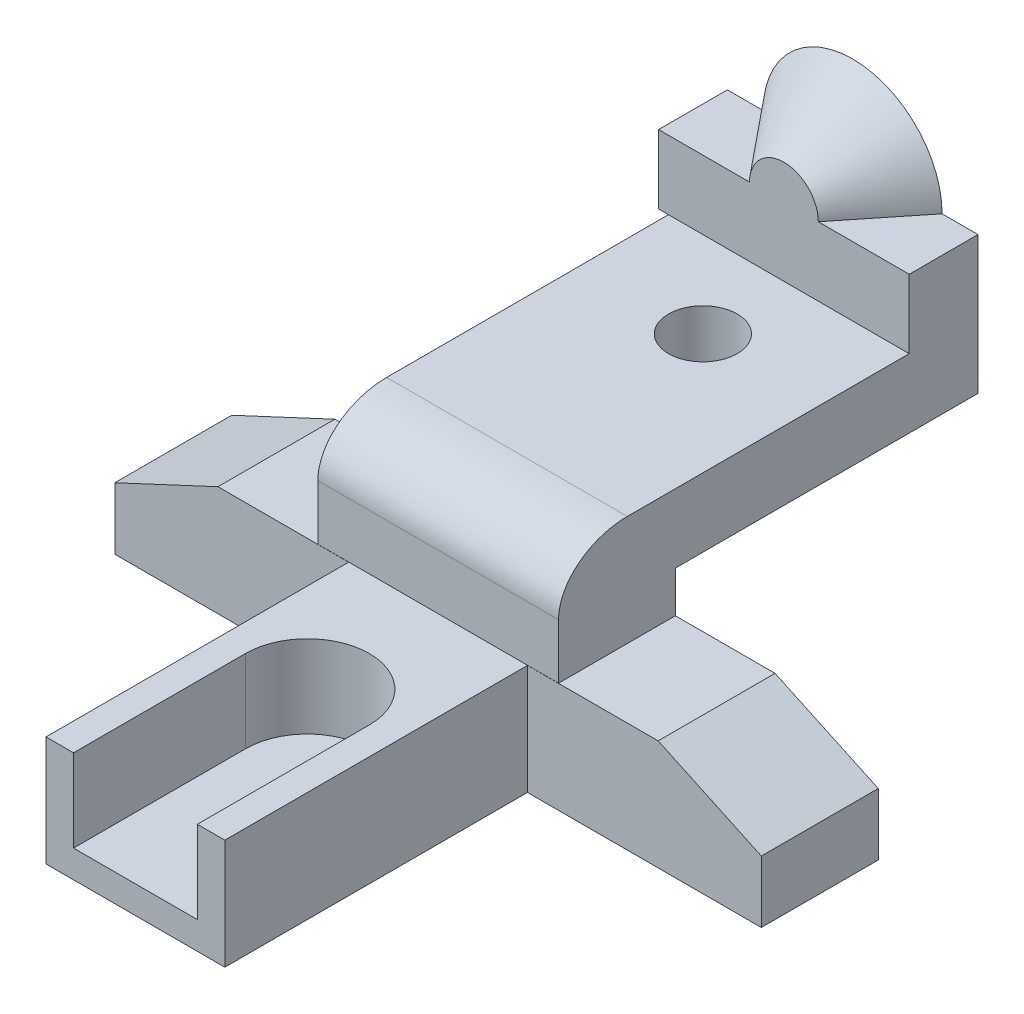
SolidWorks part; units mm, degrees
ref_plane "Plan de face" through (0, 0, 0) normal (0, 0, 1) x (1, 0, 0)
ref_plane "Plan de dessus" through (0, 0, 0) normal (0, 1, 0) x (1, 0, 0)
ref_plane "Plan de droite" through (0, 0, 0) normal (1, 0, 0) x (0, 0, -1)
sketch "Esquisse1" plane through (0, 0, 0) normal (0, 0, 1) x (1, 0, 0)
  line L0 (0, 0) -> (94, 0)
  line L1 (94, 0) -> (94, 9)
  line L2 (94, 9) -> (79, 16)
  line L3 (79, 16) -> (15, 16)
  line L4 (15, 16) -> (0, 9)
  line L5 (0, 9) -> (0, 0)
  dimension "D1" = 94
  dimension "D2" = 9
  dimension "D3" = 15
  dimension "D4" = 16
extrude "Boss.-Extru.1" add sketch "Esquisse1" against normal blind 17
sketch "Esquisse2" plane through (0, 0, 0) normal (0, 0, 1) x (1, 0, 0)
  line L0 (79, 16) -> (15, 16) construction
  line L1 (34, 16) -> (60, 16)
  line L2 (34, 16) -> (34, 0)
  line L3 (34, 0) -> (60, 0)
  line L4 (60, 16) -> (60, 0)
  line L5 (34, 16) -> (60, 0) construction
  line L6 (34, 0) -> (60, 16) construction
  line L7 (0, 0) -> (94, 0) construction
  line L8 (94, 0) -> (94, 9) construction
  point P0 (47, 8)
  point P5 (60.3546, 24.1889)
  point P6 (60.9655, 24)
  point P9 (62.1832, 0)
  point P12 (0, 0)
  dimension "D1" = 47
  dimension "D2" = 13
extrude "Boss.-Extru.2" add sketch "Esquisse2" along normal blind 44
sketch "Esquisse3" plane through (0, 16, 0) normal (0, 1, 0) x (1, 0, 0)
  line L0 (60, -44) -> (34, -44) construction
  line L1 (38, -44) -> (56, -44)
  line L2 (38, -44) -> (38, -19)
  line L4 (56, -44) -> (56, -19)
  line L5 (38, -44) -> (56, -19) construction
  line L6 (38, -19) -> (56, -44) construction
  line L7 (60, -44) -> (60, 0) construction
  arc A1 (56, -19) -> (38, -19) centre (47, -19) ccw
  point P0 (47, -31.5)
  point P6 (0, 0)
  point P7 (0, 0)
  point P8 (37.9258, -44)
  dimension "D4" = 9
  dimension "D1" = 25
  dimension "D2" = 9
  dimension "D3" = 13
extrude "Enlèv. mat.-Extru.1" cut sketch "Esquisse3" against normal blind 12
sketch "Esquisse4" plane through (0, 16, 0) normal (0, 1, 0) x (1, 0, 0)
  line L0 (79, 17) -> (15, 17) construction
  line L1 (29.5, 0.0186) -> (64.5, 0.0186)
  line L2 (29.5, 0.0186) -> (29.5, 17)
  line L3 (29.5, 17) -> (64.5, 17)
  line L4 (64.5, 0.0186) -> (64.5, 17)
  line L5 (29.5, 0.0186) -> (64.5, 17) construction
  line L6 (29.5, 17) -> (64.5, 0.0186) construction
  line L7 (79, 17) -> (79, 0) construction
  point P0 (47, 8.5093)
  point P9 (0, 0)
  dimension "D1" = 32
  dimension "D2" = 17.5
extrude "Boss.-Extru.3" add sketch "Esquisse4" along normal blind 16
sketch "Esquisse5" plane through (0, 0, -17) normal (0, 0, -1) x (-1, 0, 0)
  line L1 (-64.5, 22) -> (-29.5, 22)
  line L2 (-64.5, 22) -> (-64.5, 32)
  line L3 (-64.5, 32) -> (-29.5, 32)
  line L4 (-29.5, 22) -> (-29.5, 32)
  line L5 (-64.5, 22) -> (-29.5, 32) construction
  line L6 (-64.5, 32) -> (-29.5, 22) construction
  point P0 (-47, 27)
  point P6 (-64, 32)
  dimension "D2" = 10
extrude "Boss.-Extru.4" add sketch "Esquisse5" along normal blind 44
sketch "Esquisse6" plane through (0, 32, 0) normal (0, 1, 0) x (1, 0, 0)
  line L1 (28.0621, 51) -> (64.5, 51)
  line L2 (28.0621, 51) -> (28.0621, 61)
  line L3 (28.0621, 61) -> (64.5, 61)
  line L4 (64.5, 51) -> (64.5, 61)
  line L5 (28.0621, 51) -> (64.5, 61) construction
  line L6 (28.0621, 61) -> (64.5, 51) construction
  point P0 (46.2811, 56)
  point P6 (44.0311, 56)
  point P7 (60, 61)
  point P8 (0, 0)
  point P9 (0, 0)
  dimension "D1" = 10
extrude "Boss.-Extru.5" add sketch "Esquisse6" along normal blind 10
fillet "Congé1" radius 8 1 edges at (47, 32, -0.0186) second distance 10 first distance on face at (47, 24, -0.0186)
sketch "Esquisse8" plane through (0, 32, 0) normal (0, 1, 0) x (1, 0, 0)
  line L0 (28.0621, 51) -> (64.5, 51) construction
  circle A0 centre (47, 38.5) radius 5
  dimension "D2" = 10
  dimension "D1" = 12.5
extrude "Enlèv. mat.-Extru.2" cut sketch "Esquisse8" against normal blind 10
sketch "Esquisse9" plane through (0, 0, -51) normal (0, 0, 1) x (1, 0, 0)
  line L0 (28.0621, 42) -> (64.5, 42) construction
  line L1 (41.2811, 42) -> (51.2811, 42)
  arc A0 (51.2811, 42) -> (41.2811, 42) centre (46.2811, 42) ccw
  dimension "D1" = 5
sketch "Esquisse10" plane through (0, 0, -61) normal (0, 0, -1) x (-1, 0, 0)
  line L0 (-64.5, 42) -> (-28.0621, 42) construction
  line L1 (-33.2811, 42) -> (-59.2811, 42)
  arc A0 (-33.2811, 42) -> (-59.2811, 42) centre (-46.2811, 42) ccw
  dimension "D1" = 13
loft "Lissage2" add profiles "Esquisse9", "Esquisse10"
